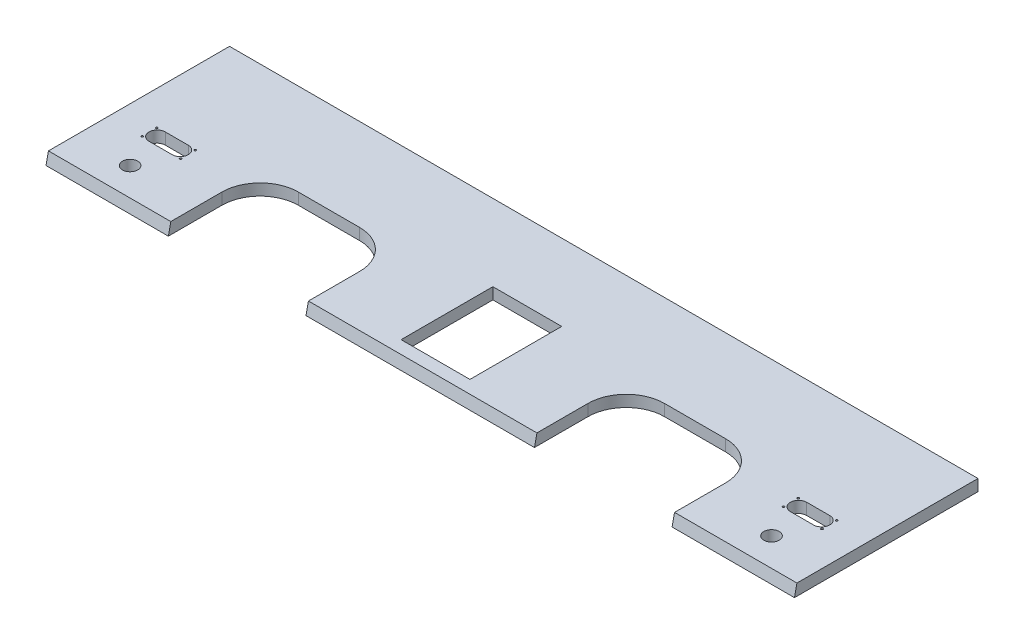
SolidWorks part; units mm, degrees
material "Beech"
ref_plane "Front Plane" through (0, 0, 0) normal (0, 0, 1) x (1, 0, 0)
ref_plane "Top Plane" through (0, 0, 0) normal (0, 1, 0) x (1, 0, 0)
ref_plane "Right Plane" through (0, 0, 0) normal (1, 0, 0) x (0, 0, -1)
sketch "Sketch1" plane through (0, 0, 0) normal (0, 1, 0) x (1, 0, 0)
  line L1 (621.5062, -152.4) -> (-621.5062, -152.4)
  line L2 (621.5062, -152.4) -> (621.5062, 152.4)
  line L3 (621.5062, 152.4) -> (-621.5062, 152.4)
  line L4 (-621.5062, -152.4) -> (-621.5062, 152.4)
  line L5 (621.5062, -152.4) -> (-621.5062, 152.4) construction
  line L6 (621.5062, 152.4) -> (-621.5062, -152.4) construction
  point P0 (0, 0)
  dimension "D1" = 1243.0125
  dimension "D2" = 304.8
extrude "Boss-Extrude1" add sketch "Sketch1" along normal blind 19.05
sketch "Sketch4" plane through (0, 19.05, 0) normal (0, 1, 0) x (1, 0, 0)
  line L0 (-621.5062, -152.4) -> (621.5062, -152.4) construction
  line L1 (189.7062, 0) -> (418.3062, -152.4) construction
  line L7 (621.5062, -152.4) -> (621.5062, 152.4) construction
  line L8 (-621.5062, 152.4) -> (-621.5062, -152.4) construction
  line L9 (-418.3062, -152.4) -> (-418.3062, -63.5)
  line L10 (-354.8062, 0) -> (-253.2062, 0)
  line L11 (-189.7062, -152.4) -> (-189.7062, -63.5)
  line L12 (-418.3062, 0) -> (-189.7062, -152.4) construction
  line L14 (189.7062, -152.4) -> (189.7062, -63.5)
  line L15 (253.2062, 0) -> (354.8062, 0)
  line L16 (418.3062, -152.4) -> (418.3062, -63.5)
  line L17 (-418.3062, -152.4) -> (-189.7062, 0) construction
  line L18 (189.7062, -152.4) -> (418.3062, 0) construction
  line L19 (-418.3062, -152.4) -> (-189.7062, -152.4)
  line L20 (189.7062, -152.4) -> (418.3062, -152.4)
  arc A0 (354.8062, 0) -> (418.3062, -63.5) centre (354.8062, -63.5) cw
  arc A1 (189.7062, -63.5) -> (253.2062, 0) centre (253.2062, -63.5) cw
  arc A2 (-253.2062, 0) -> (-189.7062, -63.5) centre (-253.2062, -63.5) cw
  arc A3 (-418.3062, -63.5) -> (-354.8062, 0) centre (-354.8062, -63.5) cw
  point P10 (304.0062, -76.2)
  point P13 (-304.0062, -76.2)
  dimension "D3" = 152.4
  dimension "D4" = 228.6
  dimension "D7" = 63.5
  dimension "D1" = 228.6
  dimension "D2" = 152.4
  dimension "D5" = 317.5
  dimension "D6" = 317.5
extrude "Cut-Extrude2" cut sketch "Sketch4" against normal through all
sketch "Sketch5" plane through (0, 19.05, 0) normal (0, 1, 0) x (1, 0, 0)
  line L1 (57.15, -127) -> (-57.15, -127)
  line L2 (57.15, -127) -> (57.15, 25.4)
  line L3 (57.15, 25.4) -> (-57.15, 25.4)
  line L4 (-57.15, -127) -> (-57.15, 25.4)
  line L5 (57.15, -127) -> (-57.15, 25.4) construction
  line L6 (57.15, 25.4) -> (-57.15, -127) construction
  line L7 (0, -152.4) -> (0, 152.4) construction
  line L8 (-189.7062, -152.4) -> (189.7062, -152.4) construction
  line L10 (-808.6756, 578.6906) -> (-805.5006, 578.6906) construction
  line L12 (0, 25.4) -> (0, -127) construction
  line L13 (621.5062, 152.4) -> (-621.5062, 152.4) construction
  point P0 (0, -50.8)
  dimension "D1" = 114.3
  dimension "D2" = 152.4
  dimension "D3" = 127
extrude "Cut-Extrude3" cut sketch "Sketch5" against normal through all
sketch "Sketch6" plane through (0, 19.05, 0) normal (0, 1, 0) x (1, 0, 0)
  line L0 (-621.5062, 152.4) -> (-621.5062, -152.4) construction
  line L1 (621.5062, 152.4) -> (-621.5062, 152.4) construction
  line L2 (621.5062, -152.4) -> (621.5062, 152.4) construction
  circle A0 centre (-532.6062, -101.6) radius 12.7
  circle A1 centre (532.6062, -101.6) radius 12.7
  dimension "D1" = 25.4
  dimension "D2" = 88.9
  dimension "D3" = 254
  dimension "D4" = 254
  dimension "D5" = 88.9
extrude "Cut-Extrude4" cut sketch "Sketch6" against normal through all
chamfer "Chamfer1" distance 19.05 angle 12 3 edges at (519.9062, 19.05, 152.4) (-519.9062, 19.05, 152.4) (0, 19.05, 152.4) first distance on face at (519.9062, 9.525, 152.4) first distance on face at (-519.9062, 9.525, 152.4) first distance on face at (0, 9.525, 152.4)
sketch "Sketch8" plane through (0, 19.05, 0) normal (0, 1, 0) x (1, 0, 0)
  line L0 (-532.6062, -148.3508) -> (-532.6062, 152.4) construction
  line L1 (-564.5062, -25.4) -> (-500.7062, -25.4) construction
  line L2 (-564.5062, -25.4) -> (-564.5062, -49.7) construction
  line L3 (-564.5062, -49.7) -> (-500.7062, -49.7) construction
  line L4 (-500.7062, -25.4) -> (-500.7062, -49.7) construction
  line L5 (-564.5062, -25.4) -> (-500.7062, -49.7) construction
  line L6 (-564.5062, -49.7) -> (-500.7062, -25.4) construction
  line L7 (621.5062, 152.4) -> (-621.5062, 152.4) construction
  line L8 (-621.5062, -148.3508) -> (-418.3062, -148.3508) construction
  line L9 (-513.4062, -37.55) -> (-551.8062, -37.55) construction
  line L10 (-513.4062, -51.05) -> (-551.8062, -51.05)
  line L11 (-513.4062, -24.05) -> (-551.8062, -24.05)
  line L12 (0, 152.4) -> (0, -148.3508) construction
  line L13 (-189.7062, -148.3508) -> (189.7062, -148.3508) construction
  line L14 (513.4062, -37.55) -> (551.8062, -37.55) construction
  line L15 (513.4062, -51.05) -> (551.8062, -51.05)
  line L16 (513.4062, -24.05) -> (551.8062, -24.05)
  line L17 (564.5062, -49.7) -> (500.7062, -25.4) construction
  line L18 (564.5062, -25.4) -> (500.7062, -49.7) construction
  line L19 (500.7062, -25.4) -> (500.7062, -49.7) construction
  line L20 (564.5062, -49.7) -> (500.7062, -49.7) construction
  line L21 (564.5062, -25.4) -> (564.5062, -49.7) construction
  line L22 (564.5062, -25.4) -> (500.7062, -25.4) construction
  circle A0 centre (-564.5062, -25.4) radius 1.65
  circle A1 centre (-564.5062, -49.7) radius 1.65
  circle A2 centre (-500.7062, -49.7) radius 1.65
  circle A3 centre (-500.7062, -25.4) radius 1.65
  arc A4 (-513.4062, -51.05) -> (-513.4062, -24.05) centre (-513.4062, -37.55) ccw
  arc A5 (-551.8062, -24.05) -> (-551.8062, -51.05) centre (-551.8062, -37.55) ccw
  arc A6 (513.4062, -51.05) -> (513.4062, -24.05) centre (513.4062, -37.55) cw
  arc A7 (551.8062, -24.05) -> (551.8062, -51.05) centre (551.8062, -37.55) cw
  circle A8 centre (500.7062, -25.4) radius 1.65
  circle A9 centre (500.7062, -49.7) radius 1.65
  circle A10 centre (564.5062, -49.7) radius 1.65
  circle A11 centre (564.5062, -25.4) radius 1.65
  point P0 (-532.6062, -37.55)
  point P11 (-532.6062, 2.0246)
  point P14 (-532.6062, -101.6)
  point P20 (-532.6062, -37.55)
  point P31 (532.6062, -37.55)
  point P44 (532.6062, -101.6)
  point P45 (532.6062, 2.0246)
  dimension "D4" = 3.3
  dimension "D1" = 63.8
  dimension "D2" = 24.3
  dimension "D3" = 177.8
  dimension "D5" = 38.4
  dimension "D6" = 27
extrude "Cut-Extrude5" cut sketch "Sketch8" against normal through all
